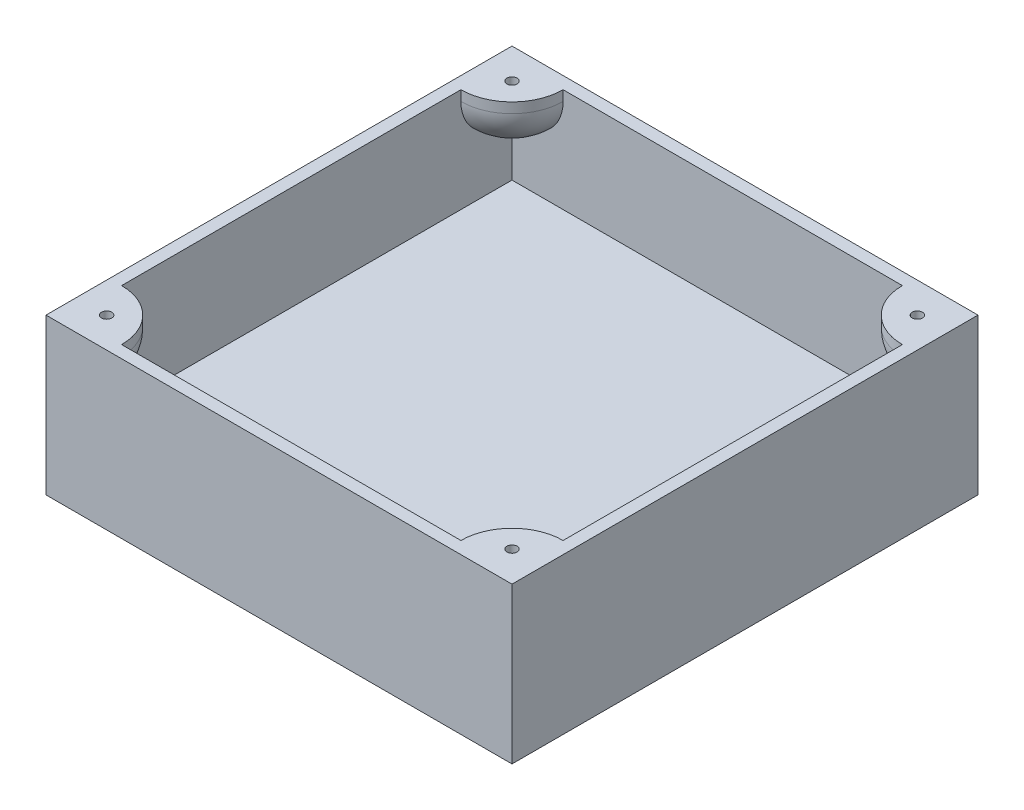
SolidWorks part; units mm, degrees
ref_plane "Front Plane" through (0, 0, 0) normal (0, 0, 1) x (1, 0, 0)
ref_plane "Top Plane" through (0, 0, 0) normal (0, 1, 0) x (1, 0, 0)
ref_plane "Right Plane" through (0, 0, 0) normal (1, 0, 0) x (0, 0, -1)
sketch "Sketch1" plane through (0, 0, 0) normal (0, 1, 0) x (1, 0, 0)
  line L0 (-108, -108) -> (-108, 108)
  line L1 (-114, -114) -> (114, -114)
  line L2 (-114, -114) -> (-114, 114)
  line L3 (-114, 114) -> (114, 114)
  line L4 (114, -114) -> (114, 114)
  line L5 (-108, 108) -> (108, 108)
  line L6 (108, -108) -> (108, 108)
  line L7 (-108, -108) -> (108, -108)
  point P0 (0, 0)
  point P6 (0, 114)
  point P7 (-114, 0)
  point P12 (0, 0)
  dimension "D1" = 228
  dimension "D2" = 228
  dimension "D3" = 6
extrude "Base" add sketch "Sketch1" along normal blind 25.4 contours L1 L4 L3 L2
extrude "Walls" add sketch "Sketch1<3>" along normal blind 50.8 from surface starting at face at (0, 25.4, 0)
sketch "Sketch1<3>" plane through (0, 0, 0) normal (0, 1, 0) x (1, 0, 0) same geometry as "Sketch1"
sketch "Sketch2" plane through (0, 76.2, 0) normal (0, 1, 0) x (1, 0, 0)
  line L0 (-108, 108) -> (-108, 83)
  line L1 (-108, 108) -> (-108, -108) construction
  line L2 (-108, 108) -> (-83, 108)
  line L3 (108, 108) -> (-108, 108) construction
  line L4 (-41.91, 0) -> (41.91, 0) construction
  line L7 (-108, -108) -> (-108, -83)
  line L12 (-108, 108) -> (-90.3223, 90.3223) construction
  line L13 (-108, -108) -> (-83, -108)
  line L14 (0, -41.91) -> (0, 41.91) construction
  line L15 (108, -108) -> (83, -108)
  line L16 (108, -108) -> (108, -83)
  line L17 (108, 108) -> (108, 83)
  line L18 (108, 108) -> (83, 108)
  arc A0 (-108, 83) -> (-83, 108) centre (-108, 108) ccw
  circle A4 centre (-99.1612, 99.1612) radius 2.5
  circle A5 centre (-99.1612, -99.1612) radius 2.5
  arc A6 (-108, -83) -> (-83, -108) centre (-108, -108) cw
  circle A7 centre (99.1612, -99.1612) radius 2.5
  arc A8 (108, -83) -> (83, -108) centre (108, -108) ccw
  circle A9 centre (99.1612, 99.1612) radius 2.5
  arc A10 (108, 83) -> (83, 108) centre (108, 108) cw
  dimension "D2" = 5
  dimension "D1" = 25
extrude "ScrewMounts" add sketch "Sketch2" against normal blind 25 contours L17 A10 L18 | L15 A8 L16 | A0 L2 L0 | L7 A6 L13
extrude "ScrewHoles" cut sketch "Sketch2<5>" against normal blind 12.5 contours A7 | A9 | A5 | A4
sketch "Sketch2<5>" plane through (0, 76.2, 0) normal (0, 1, 0) x (1, 0, 0) same geometry as "Sketch2"
fillet "Fillet1" radius 20 4 edges at (-90.3223, 51.2, -90.3223) (-90.3223, 51.2, 90.3223) (90.3223, 51.2, 90.3223) (90.3223, 51.2, -90.3223)
